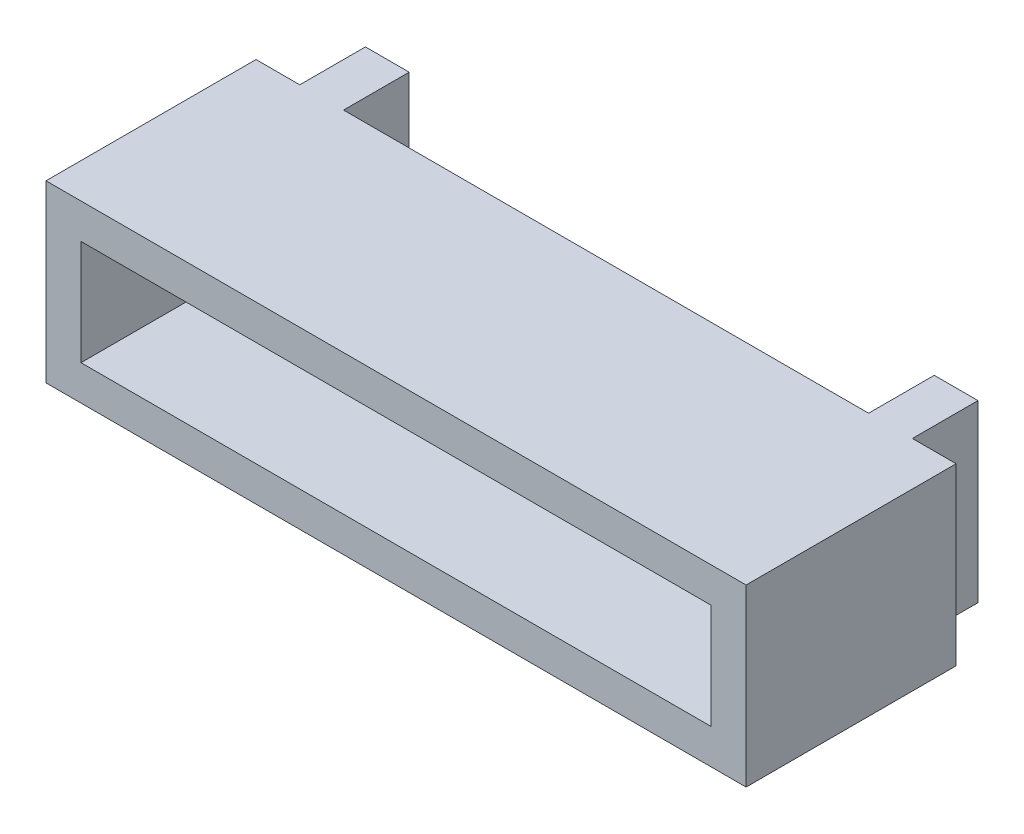
SolidWorks part; units mm, degrees
ref_plane "Front Plane" through (0, 0, 0) normal (0, 0, 1) x (1, 0, 0)
ref_plane "Top Plane" through (0, 0, 0) normal (0, 1, 0) x (1, 0, 0)
ref_plane "Right Plane" through (0, 0, 0) normal (1, 0, 0) x (0, 0, -1)
sketch "Sketch1" plane through (0, 0, 0) normal (0, 1, 0) x (1, 0, 0)
  line L0 (-16, 0) -> (16, 0)
  line L8 (-16, 0) -> (-16, 9.6)
  line L9 (-16, 9.6) -> (-14, 9.6)
  line L10 (-14, 9.6) -> (-14, 12.6)
  line L11 (-14, 12.6) -> (-12, 12.6)
  line L12 (-12, 12.6) -> (-12, 9.6)
  line L13 (-12, 9.6) -> (12, 9.6)
  line L14 (12, 9.6) -> (12, 12.6)
  line L15 (12, 12.6) -> (14, 12.6)
  line L16 (14, 12.6) -> (14, 9.6)
  line L17 (14, 9.6) -> (16, 9.6)
  line L18 (16, 9.6) -> (16, 0)
  point P4 (0, 0)
  dimension "D1" = 32
  dimension "D2" = 9.6
  dimension "D3" = 3
  dimension "D4" = 2
  dimension "D5" = 2
extrude "Boss-Extrude1" add sketch "Sketch1" along normal blind 8
sketch "Sketch2" plane through (0, 0, -9.6) normal (0, 0, -1) x (-1, 0, 0)
  line L0 (-16, 4) -> (-4, 4) construction
  line L2 (-4, 4) -> (4, 4) construction
  line L4 (-16, 8) -> (-16, 0) construction
  circle A0 centre (4, 4) radius 2.4
  circle A1 centre (-4, 4) radius 2.4
  dimension "D2" = 4.8
  dimension "D3" = 4.8
  dimension "D1" = 8
  dimension "D4" = 12
extrude "Boss-Extrude2" add sketch "Sketch2" along normal blind 1.6
shell "Shell1" thickness 1.6 removed face at (0, 4, 0)
